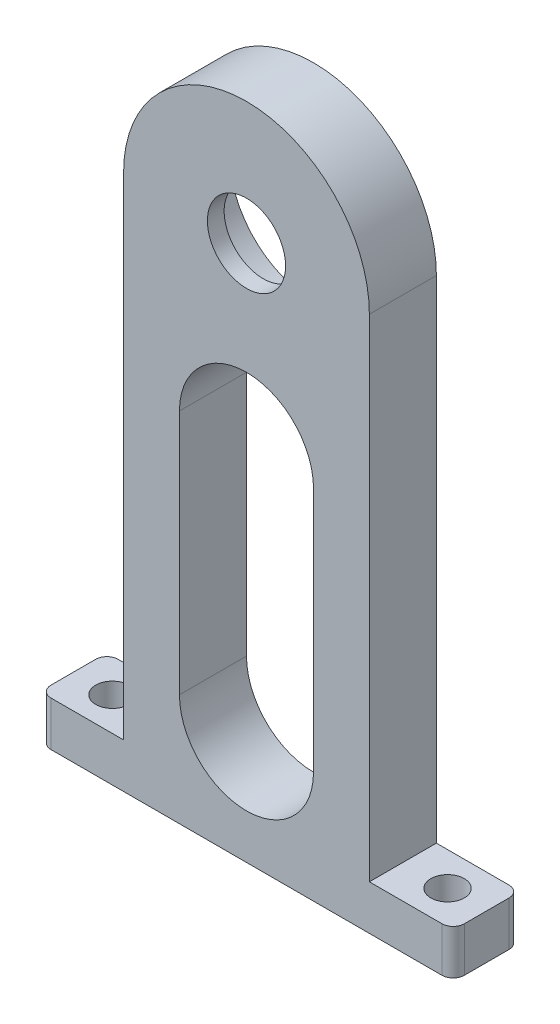
SolidWorks part; units mm, degrees
ref_plane "Front Plane" through (0, 0, 0) normal (0, 0, 1) x (1, 0, 0)
ref_plane "Top Plane" through (0, 0, 0) normal (0, 1, 0) x (1, 0, 0)
ref_plane "Right Plane" through (0, 0, 0) normal (1, 0, 0) x (0, 0, -1)
sketch "Sketch1" plane through (0, 0, 0) normal (0, 0, 1) x (1, 0, 0)
  line L0 (22, 0) -> (22, -88)
  line L1 (22, -88) -> (37, -88)
  line L2 (37, -88) -> (37, -96)
  line L3 (37, -96) -> (-37, -96)
  line L4 (-37, -96) -> (-37, -88)
  line L5 (-37, -88) -> (-22, -88)
  line L6 (-22, -88) -> (-22, 0)
  line L7 (0, -32) -> (0, -76) construction
  line L8 (12, -32) -> (12, -76)
  line L9 (-12, -32) -> (-12, -76)
  circle A0 centre (0, 0) radius 15
  circle A1 centre (0, 0) radius 7
  arc A2 (22, 0) -> (-22, 0) centre (0, 0) ccw
  arc A3 (12, -32) -> (-12, -32) centre (0, -32) ccw
  arc A4 (-12, -76) -> (12, -76) centre (0, -76) ccw
  point P13 (0, -54)
  dimension "D1" = 14
  dimension "D2" = 30
  dimension "D3" = 44
  dimension "D4" = 96
  dimension "D5" = 15
  dimension "D6" = 8
  dimension "D7" = 15
  dimension "D8" = 44
  dimension "D9" = 24
  dimension "D10" = 12
  dimension "D11" = 8
extrude "Boss-Extrude2" add sketch "Sketch1" along normal blind 12 contours L0 A2 L6 L5 L4 L3 L2 L1 A4 L9 A3 L8 A0 | A0 A1 region at (20.6072, -44, 0) region at (-14.5757, 0, 0)
sketch "Sketch3" plane through (0, -96, 0) normal (0, -1, 0) x (1, 0, 0)
  line L0 (37, 0) -> (-37, 0) construction
  circle A0 centre (-30, 6) radius 3
  circle A1 centre (30, 6) radius 3
  dimension "D1" = 6
  dimension "D4" = 6
  dimension "D2" = 30
  dimension "D3" = 30
  dimension "D5" = 6
  dimension "D6" = 6
extrude "Cut-Extrude1" cut sketch "Sketch3" against normal through all
extrude "Cut-Extrude2" cut sketch "Sketch1<4>" along normal blind 9 contours A0 A1 region at (-14.5757, 0, 0)
sketch "Sketch1<4>" plane through (0, 0, 0) normal (0, 0, 1) x (1, 0, 0) same geometry as "Sketch1"
fillet "Fillet1" radius 2 4 edges at (-37, -92, 0) (-37, -92, 12) (37, -92, 0) (37, -92, 12)
